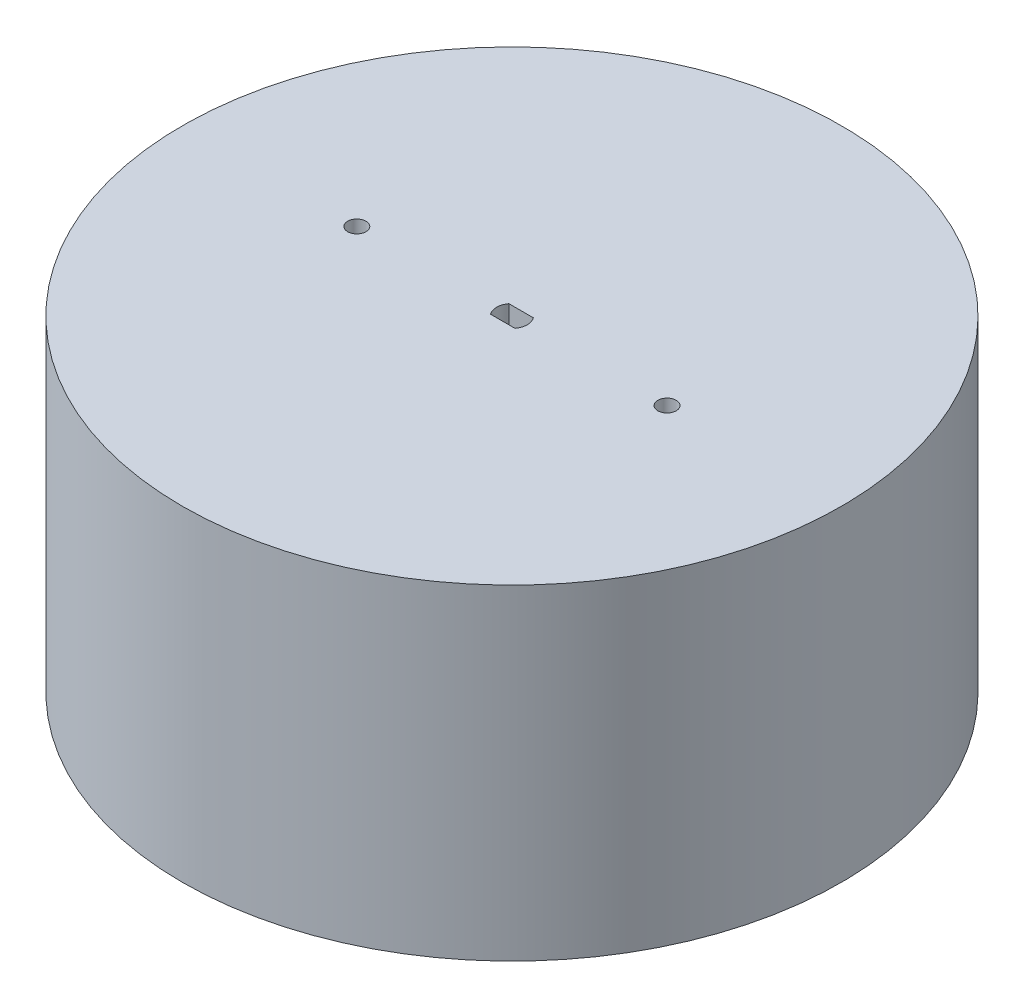
SolidWorks part; units mm, degrees
ref_plane "Front Plane" through (0, 0, 0) normal (0, 0, 1) x (1, 0, 0)
ref_plane "Top Plane" through (0, 0, 0) normal (0, 1, 0) x (1, 0, 0)
ref_plane "Right Plane" through (0, 0, 0) normal (1, 0, 0) x (0, 0, -1)
sketch "Sketch1" plane through (0, 0, 0) normal (0, 1, 0) x (1, 0, 0)
  circle A0 centre (0, 0) radius 47.625
  circle A1 centre (0, 0) radius 53.975
  dimension "D1" = 95.25
  dimension "D2" = 107.95
extrude "Boss-Extrude1" add sketch "Sketch1" along normal blind 8.89 contours A0 | A1 A0 region at (0, 0, 0) region at (-52.4484, 0, 0)
extrude "Boss-Extrude2" add sketch "Sketch1<4>" against normal blind 44.45
sketch "Sketch1<4>" plane through (0, 0, 0) normal (0, 1, 0) x (1, 0, 0) same geometry as "Sketch1"
sketch "Sketch2" plane through (0, 8.89, 0) normal (0, 1, 0) x (1, 0, 0)
  line L0 (-2, 1.5) -> (2, 1.5)
  line L1 (-2, -1.5) -> (2, -1.5)
  arc A0 (2, 1.5) -> (2, -1.5) centre (0, 0) cw
  arc A1 (-2, 1.5) -> (-2, -1.5) centre (0, 0) ccw
  point P6 (0, 0)
extrude "Cut-Extrude1" cut sketch "Sketch2" against normal blind 25.4
sketch "Sketch3" plane through (0, 0, 0) normal (0, -1, 0) x (1, 0, 0)
  circle A0 centre (0, 0) radius 34.925
  circle A1 centre (0, 0) radius 47.625
  circle A2 centre (0, 0) radius 47.625 construction
  dimension "3" = 69.85
extrude "Boss-Extrude3" add sketch "Sketch3" along normal blind 3.4925
sketch "Sketch4" plane through (0, 8.89, 0) normal (0, 1, 0) x (1, 0, 0)
  circle A0 centre (25.4, 0) radius 1.5
  circle A1 centre (-25.4, 0) radius 1.5
  point P4 (0, 0)
  dimension "D1" = 3
  dimension "D2" = 25.4
  dimension "D3" = 25.4
extrude "Cut-Extrude2" cut sketch "Sketch4" against normal blind 21.2725
